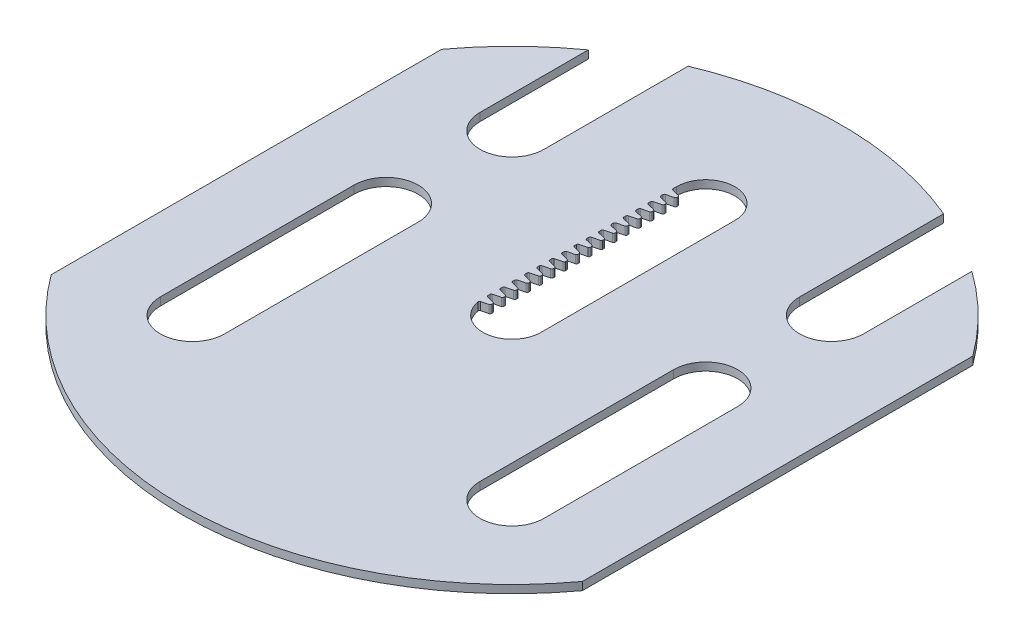
SolidWorks part; units mm, degrees
ref_plane "Front Plane" through (0, 0, 0) normal (0, 0, 1) x (1, 0, 0)
ref_plane "Top Plane" through (0, 0, 0) normal (0, 1, 0) x (1, 0, 0)
ref_plane "Right Plane" through (0, 0, 0) normal (1, 0, 0) x (0, 0, -1)
sketch "Sketch3" plane through (0, 0, 0) normal (0, -1, 0) x (1, 0, 0)
  line L0 (0, 0) -> (0, -38.4328) construction
  line L1 (5.8, 0) -> (5.8, -38.4328)
  line L2 (-5.8, 0) -> (-5.8, -38.4328)
  line L3 (-31.7055, -70.1383) -> (31.7055, -6.7274) construction
  line L4 (-31.7055, -6.7274) -> (31.7055, -70.1383) construction
  line L5 (-31.7055, -6.7274) -> (31.7055, -6.7274) construction
  line L6 (-31.7055, -6.7274) -> (-31.7055, 31.7055) construction
  line L7 (-38.0755, -6.7274) -> (-38.0755, 31.7055)
  line L8 (-25.3355, -6.7274) -> (-25.3355, 31.7055)
  line L9 (-31.7055, -70.1383) -> (-31.7055, -31.7055) construction
  line L10 (-38.0555, -70.1383) -> (-38.0555, -31.7055)
  line L11 (-25.3555, -70.1383) -> (-25.3555, -31.7055)
  line L12 (31.7055, -6.7274) -> (31.7055, 31.7055) construction
  line L13 (25.3555, -6.7274) -> (25.3555, 31.7055)
  line L14 (38.0555, -6.7274) -> (38.0555, 31.7055)
  line L15 (31.7055, -70.1383) -> (31.7055, -31.7055) construction
  line L16 (25.3555, -70.1383) -> (25.3555, -31.7055)
  line L17 (38.0555, -70.1383) -> (38.0555, -31.7055)
  circle A0 centre (0, 0) radius 65.405
  arc A1 (5.8, 0) -> (-5.8, 0) centre (0, 0) ccw
  arc A2 (-5.8, -38.4328) -> (5.8, -38.4328) centre (0, -38.4328) ccw
  arc A3 (-38.0755, -6.7274) -> (-25.3355, -6.7274) centre (-31.7055, -6.7274) ccw
  arc A4 (-25.3355, 31.7055) -> (-38.0755, 31.7055) centre (-31.7055, 31.7055) ccw
  arc A5 (-38.0555, -70.1383) -> (-25.3555, -70.1383) centre (-31.7055, -70.1383) ccw
  arc A6 (-25.3555, -31.7055) -> (-38.0555, -31.7055) centre (-31.7055, -31.7055) ccw
  arc A7 (25.3555, -6.7274) -> (38.0555, -6.7274) centre (31.7055, -6.7274) ccw
  arc A8 (38.0555, 31.7055) -> (25.3555, 31.7055) centre (31.7055, 31.7055) ccw
  arc A9 (25.3555, -70.1383) -> (38.0555, -70.1383) centre (31.7055, -70.1383) ccw
  arc A10 (38.0555, -31.7055) -> (25.3555, -31.7055) centre (31.7055, -31.7055) ccw
  point P5 (0, -19.2164)
  point P10 (-31.7055, 12.4891)
  point P13 (0, -38.4328)
  point P16 (0, -38.4328)
  point P22 (-31.7055, -50.9219)
  point P28 (31.7055, 12.4891)
  point P34 (31.7055, -50.9219)
  dimension "D1" = 130.81
  dimension "D3" = 5.8
  dimension "D8" = 6.37
  dimension "D10" = 6.35
  dimension "D13" = 6.35
  dimension "D14" = 6.35
  dimension "D2" = 38.4328
  dimension "D4" = 45
  dimension "D5" = 45
  dimension "D6" = 89.6766
extrude "Boss-Extrude1" add sketch "Sketch3" along normal blind 1.5875 contours L17 A10 L16 A0 L11 A6 L10 L2 A2 L1 A1 L8 A4 L7 A3 L14 A8 L13 A7 region at (-29.0606, 0, 56.5219)
sketch "Sketch4" plane through (0, 0, 0) normal (0, 1, 0) x (1, 0, 0)
  line L0 (-5.8, 0) -> (-3.94, 0) construction
  line L1 (-3.94, -0.34) -> (-3.94, 0.34)
  line L2 (-3.94, 0.34) -> (-5.8, 0.8038)
  line L3 (-5.8, 0) -> (-5.8, 38.4328) construction
  line L8 (-5.8, 0.8038) -> (-5.8, -0.8038)
  line L9 (-5.8, -0.8038) -> (-3.94, -0.34)
  point P7 (-3.94, 0)
  line M5 (-5.8, 0) -> (-5.8, 38.4328)
  arc M8 (5.8, 0) -> (-5.8, 0) centre (0, 0) cw
  dimension "D3" = 76
  dimension "D1" = 1.86
  dimension "D2" = 0.34
extrude "Boss-Extrude2" add sketch "Sketch4" against normal up to surface (1.5875 mm away) contours L1 L2 M5 M8 | L0 L9 L1 M8 | L8 L9 M8 region at (-4.9957, 0, -0.3016) region at (-5.7837, 0, 0.5979) region at (-4.9847, 0, 0.2975) up to face at (0, -1.5875, -19.2164)
pattern_linear "LPattern1" count 16 spacing 2.45 along (0, 0, -1) of "Boss-Extrude2"
fillet "Fillet1" radius 0.3 64 edges at (-3.94, -0.7937, 0.34) (-5.8, -0.7937, -1.6462) (-3.94, -0.7937, -2.11) (-3.94, -0.7937, -2.79) (-5.8, -0.7937, -3.2538) (-5.8, -0.7937, -4.0962) (-3.94, -0.7937, -4.56) (-3.94, -0.7937, -5.24) (-5.8, -0.7937, -5.7038) (-5.8, -0.7937, -6.5462) (-3.94, -0.7937, -7.01) (-3.94, -0.7937, -7.69) (-5.8, -0.7937, -8.1538) (-5.8, -0.7937, -8.9962) (-3.94, -0.7937, -9.46) (-3.94, -0.7937, -10.14) (-5.8, -0.7937, -10.6038) (-5.8, -0.7937, -11.4462) (-3.94, -0.7937, -11.91) (-3.94, -0.7937, -12.59) (-5.8, -0.7937, -13.0538) (-5.8, -0.7937, -13.8962) (-3.94, -0.7937, -14.36) (-3.94, -0.7937, -15.04) (-5.8, -0.7937, -15.5038) (-5.8, -0.7937, -16.3462) (-3.94, -0.7937, -16.81) (-3.94, -0.7937, -17.49) (-5.8, -0.7937, -17.9538) (-5.8, -0.7937, -18.7962) (-3.94, -0.7937, -19.26) (-3.94, -0.7937, -19.94) (-5.8, -0.7937, -20.4038) (-5.7459, -0.7937, 0.7903) (-5.8, -0.7937, -0.8038) (-3.94, -0.7937, -0.34) (-3.94, -0.7937, -21.71) (-3.94, -0.7937, -22.39) (-5.8, -0.7937, -22.8538) (-5.8, -0.7937, -23.6962) (-3.94, -0.7937, -24.16) (-3.94, -0.7937, -24.84) (-5.8, -0.7937, -25.3038) (-5.8, -0.7937, -26.1462) (-3.94, -0.7937, -26.61) (-3.94, -0.7937, -27.29) (-5.8, -0.7937, -27.7538) (-5.8, -0.7937, -28.5962) (-3.94, -0.7937, -29.06) (-3.94, -0.7937, -29.74) (-5.8, -0.7937, -21.2462) (-5.8, -0.7937, -35.9462) (-3.94, -0.7937, -36.41) (-5.8, -0.7937, -37.5538) (-3.94, -0.7937, -37.09) (-5.8, -0.7937, -35.1038) (-3.94, -0.7937, -34.64) (-3.94, -0.7937, -33.96) (-5.8, -0.7937, -33.4962) (-5.8, -0.7937, -32.6538) (-3.94, -0.7937, -32.19) (-3.94, -0.7937, -31.51) (-5.8, -0.7937, -31.0462) (-5.8, -0.7937, -30.2038)
sketch "Sketch5" plane through (0, 0, 0) normal (0, 1, 0) x (1, 0, 0)
  line L1 (-65.405, 38.7298) -> (-52.705, 38.7298)
  line L2 (-65.405, 38.7298) -> (-65.405, -38.7298)
  line L3 (-65.405, -38.7298) -> (-52.705, -38.7298)
  line L4 (-52.705, 38.7298) -> (-52.705, -38.7298)
  line L5 (-65.405, 38.7298) -> (-52.705, -38.7298) construction
  line L6 (-65.405, -38.7298) -> (-52.705, 38.7298) construction
  arc A0 (-38.0555, 53.1939) -> (38.0555, 53.1939) centre (0, 0) ccw construction
  point P0 (-59.055, 0)
  point P8 (0, 0)
  dimension "D1" = 12.7
extrude "Cut-Extrude1" cut sketch "Sketch5" against normal through all
mirror "Mirror1" about plane through (0, 0, 0) normal (1, 0, 0) of "Cut-Extrude1"
